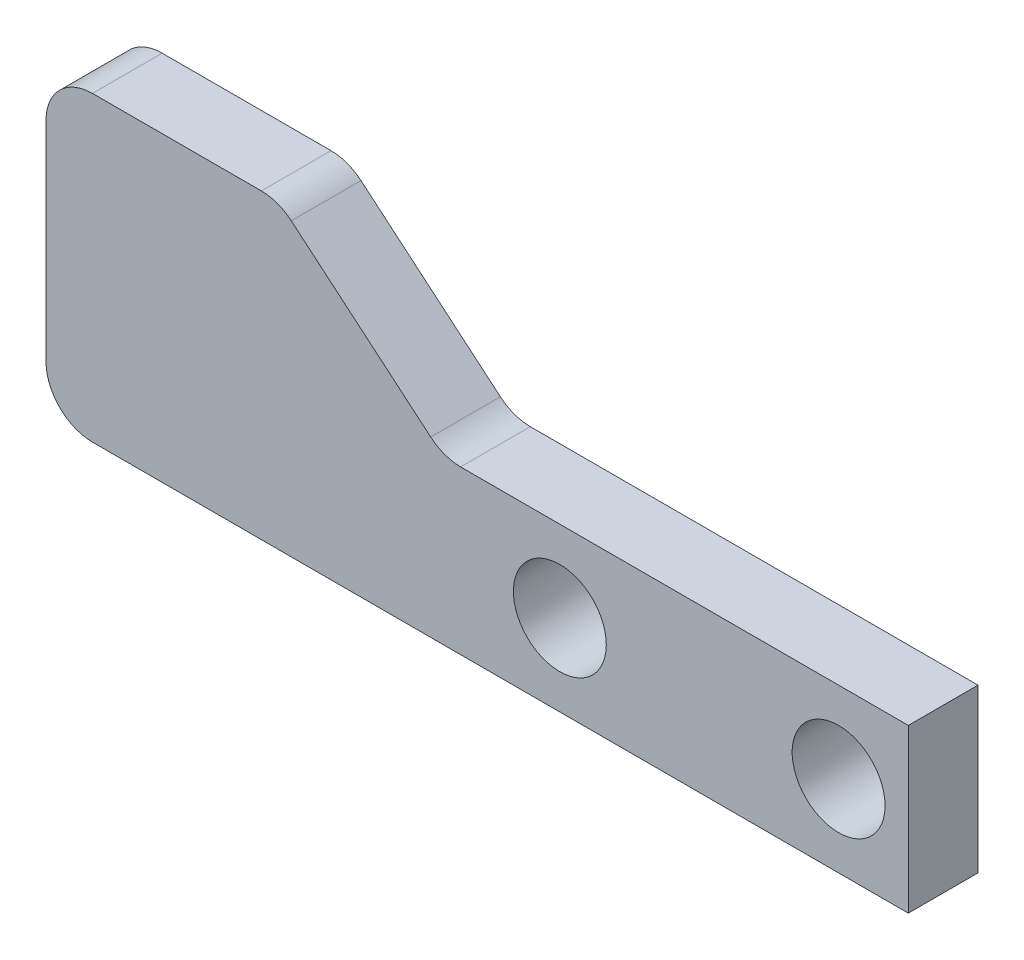
SolidWorks part; units mm, degrees
ref_plane "Front Plane" through (0, 0, 0) normal (0, 0, 1) x (1, 0, 0)
ref_plane "Top Plane" through (0, 0, 0) normal (0, 1, 0) x (1, 0, 0)
ref_plane "Right Plane" through (0, 0, 0) normal (1, 0, 0) x (0, 0, -1)
sketch "Sketch1" plane through (0, 0, 0) normal (0, 0, 1) x (1, 0, 0)
  line L0 (0, 8.6103) -> (0, -11.7685) construction
  line L1 (-9, -3.5) -> (9, -3.5)
  line L2 (-9, -3.5) -> (-9, 3.5) construction
  line L3 (-9, 3.5) -> (9, 3.5)
  line L4 (9, -3.5) -> (9, 3.5)
  line L5 (-9, -3.5) -> (9, 3.5) construction
  line L6 (-9, 3.5) -> (9, -3.5) construction
  line L7 (-9, 3.5) -> (-10.2694, 3.5)
  line L8 (-11.5586, 3.9709) -> (-17.5586, 9.0291)
  line L9 (-18.8477, 9.5) -> (-26.1171, 9.5)
  line L10 (-28.1171, 7.5) -> (-28.1171, -1.5)
  line L11 (-26.1171, -3.5) -> (-9, -3.5)
  circle A0 centre (-6, 0) radius 2
  circle A1 centre (6, 0) radius 2
  arc A2 (-26.1171, -3.5) -> (-28.1171, -1.5) centre (-26.1171, -1.5) cw
  arc A3 (-28.1171, 7.5) -> (-26.1171, 9.5) centre (-26.1171, 7.5) cw
  arc A4 (-10.2694, 3.5) -> (-11.5586, 3.9709) centre (-10.2694, 5.5) cw
  arc A5 (-18.8477, 9.5) -> (-17.5586, 9.0291) centre (-18.8477, 7.5) cw
  point P0 (0, 0)
  point P18 (-28.1171, -3.5)
  point P21 (-28.1171, 9.5)
  point P24 (-11, 3.5)
  point P27 (-18.1171, 9.5)
  dimension "D1" = 4
  dimension "D9" = 2
  dimension "D10" = 2
  dimension "D11" = 2
  dimension "D2" = 12
  dimension "D3" = 18
  dimension "D4" = 7
  dimension "D5" = 6
  dimension "D6" = 2
  dimension "D7" = 6
  dimension "D8" = 10
extrude "Boss-Extrude1" add sketch "Sketch1" along normal mid plane 3
sketch "Sketch2" plane through (0, 0, 1.5) normal (0, 0, 1) x (1, 0, 0)
  line L0 (-28.1171, 7.5) -> (-28.1171, -1.5) construction
  line L1 (9, -3.5) -> (-26.1171, -3.5)
  line L2 (9, -3.5) -> (9, -1.5)
  line L3 (9, -1.5) -> (9.2726, -1.5)
  line L4 (-9.2726, -1.5) -> (-28.1171, -1.5)
  line L5 (9, 3.5) -> (-28.1171, 3.5)
  line L6 (9, 3.5) -> (9, 1.5)
  line L7 (9, 1.5) -> (9.2726, 1.5)
  line L8 (-28.1171, 3.5) -> (-28.1171, 1.5)
  line L9 (-9.2726, 1.5) -> (-28.1171, 1.5)
  line L10 (2.7274, -1.5) -> (-2.7274, -1.5)
  line L11 (2.7274, 1.5) -> (-2.7274, 1.5)
  arc A0 (-9.2726, -1.5) -> (-2.7274, -1.5) centre (-6, 0) ccw
  arc A1 (9.2726, 1.5) -> (2.7274, 1.5) centre (6, 0) ccw
  arc A2 (-28.1171, -1.5) -> (-26.1171, -3.5) centre (-26.1171, -1.5) ccw
  arc A3 (-2.7274, 1.5) -> (-9.2726, 1.5) centre (-6, 0) ccw
  arc A4 (2.7274, -1.5) -> (9.2726, -1.5) centre (6, 0) ccw
  dimension "D1" = 7.2
  dimension "D2" = 2
  dimension "D3" = 2
extrude "Boss-Extrude2" add sketch "Sketch2" along normal blind 2 rebuild error yes
